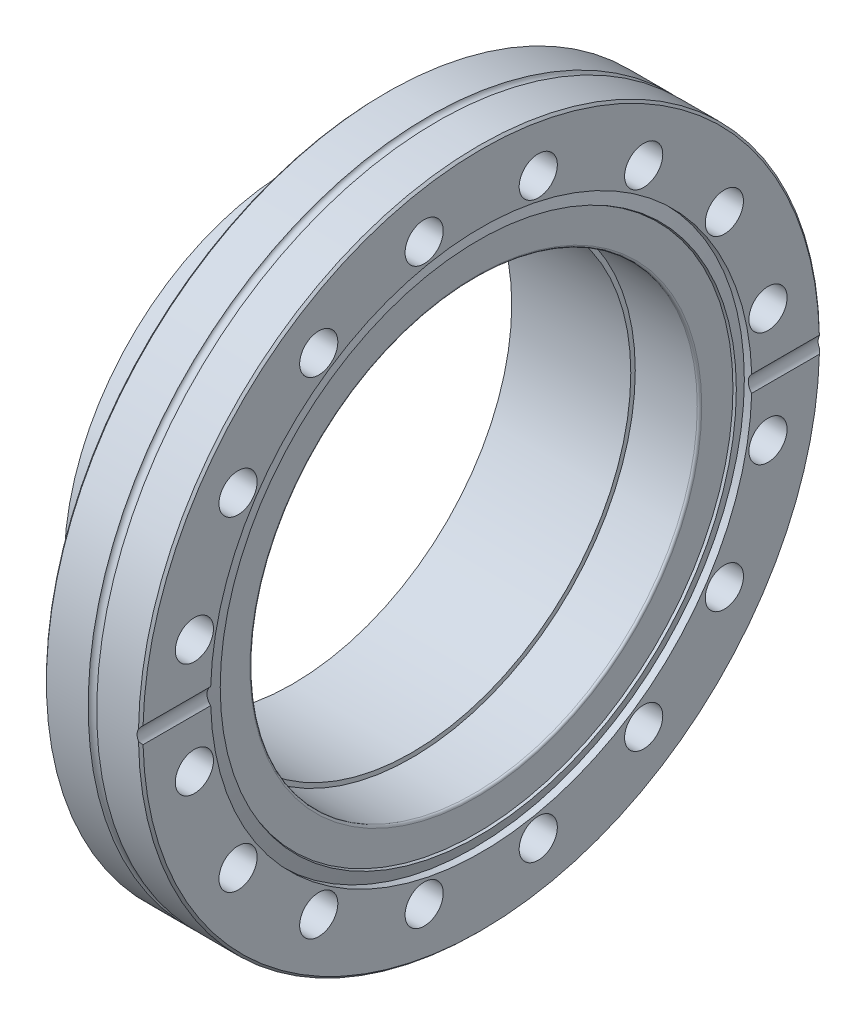
SolidWorks part; units mm, degrees
material "AISI 304"
ref_plane "Спереди" through (0, 0, 0) normal (0, 0, 1) x (1, 0, 0)
ref_plane "Сверху" through (0, 0, 0) normal (0, 1, 0) x (1, 0, 0)
ref_plane "Справа" through (0, 0, 0) normal (1, 0, 0) x (0, 0, -1)
ref_axis "Ось1" through (-110.1507, 0, 0) along (1, 0, 0)
sketch "Эскиз1" plane through (0, 0, 0) normal (0, 0, 1) x (1, 0, 0)
  line L0 (0, 75.8) -> (0, 0) construction
  line L1 (0, 0) -> (-21.85, 0) construction
  line L2 (-21.35, 75.8) -> (-12.0539, 75.8)
  line L3 (-0.35, 75.3) -> (-0.35, 60.25)
  line L4 (-0.35, 60.25) -> (-2.0191, 60.25)
  line L5 (-2.0191, 60.25) -> (-1, 57.45)
  line L6 (-1, 57.45) -> (-1.55, 57.2498)
  line L7 (-1.55, 57.2498) -> (-1.55, 50.3)
  line L8 (-2.05, 49.8) -> (-15.85, 49.8)
  line L9 (-15.85, 49.8) -> (-15.85, 51)
  line L10 (-15.85, 51) -> (-21.85, 51)
  line L11 (-21.85, 51) -> (-21.85, 75.3)
  line L12 (-10.1461, 75.8) -> (-0.85, 75.8)
  line L13 (-21.85, 75.3) -> (-21.35, 75.8)
  line L14 (-0.85, 75.8) -> (-0.35, 75.3)
  line L15 (-21.85, 65.1) -> (-0.35, 65.1) construction
  line L16 (-15.85, 50.8) -> (-135.35, 50.8)
  line L17 (-135.35, 50.8) -> (-135.35, 48.8)
  line L18 (-135.35, 48.8) -> (-15.85, 48.8)
  line L19 (-15.85, 48.8) -> (-15.85, 49.8)
  arc A0 (-12.0539, 75.8) -> (-10.1461, 75.8) centre (-11.1, 76.1) ccw
  arc A1 (-1.55, 50.3) -> (-2.05, 49.8) centre (-2.05, 50.3) cw
  point P4 (-21.85, 75.8)
  point P5 (-0.35, 75.8)
  point P14 (-21.85, 51)
  dimension "D2" = 1
  dimension "D18" = 0.5
  dimension "D1" = 151.6
  dimension "D3" = 10.75
  dimension "D4" = 0.3
  dimension "D5" = 21.5
  dimension "D6" = 102
  dimension "D7" = 6
  dimension "D8" = 20
  dimension "D9" = 120.5
  dimension "D10" = 0.65
  dimension "D11" = 114.9
  dimension "D12" = 1.2
  dimension "D13" = 99.6
  dimension "D14" = 0.5
  dimension "D15" = 45
  dimension "D16" = 0.5
  dimension "D17" = 45
  dimension "D19" = 101.6
  dimension "D20" = 135
  dimension "D21" = 130.2
  dimension "D22" = 2
  dimension "D23" = 2
revolve "Повернуть2" add sketch "Эскиз1" angle 360 about L1 region at (-11.2305, 63.1166, 0)
sketch "Эскиз7" plane through (-0.35, 0, 0) normal (1, 0, 0) x (0, 0, -1)
  line L0 (0, 0) -> (0, 65.1) construction
  line L1 (12.7004, 63.8491) -> (0, 0) construction
  circle A0 centre (0, 0) radius 65.1
  dimension "D1" = 11.25
hole_wizard "Отверстие с зазором M81" positions "Эскиз3" profile "Эскиз2" hole size "M8" standard "DIN" end condition through all
sketch "Эскиз3" plane through (-0.35, 0, 0) normal (1, 0, 0) x (0, 0, -1)
  point P3 (12.7004, 63.8491)
sketch "Эскиз2" plane through (-0.35, 63.8491, -12.7004) normal (0, 1, 0) x (0, 0, -1)
  line L0 (0, 0) -> (0, 21.5)
  line L1 (0, 21.5) -> (4.275, 21.5)
  line L2 (4.25, 21.475) -> (4.25, 0)
  line L5 (4.25, 0) -> (0, 0)
  line L7 (4.275, 21.5) -> (4.25, 21.475)
  line L8 (-4.275, 21.5) -> (-4.25, 21.475) construction
  line L11 (0, -6.35) -> (0, 107.95) construction
  dimension "Диаметр сквозного отверстия" = 8.5
  dimension "Глубина сквозного отверстия" = 21.5
  dimension "Диаметр задней зенковки" = 8.55
  dimension "Угол задней зенковки" = 90
pattern_circular "Круговой массив1" count 16 over 360 about axis through (-110.1507, 0, 0) along (1, 0, 0) of "Отверстие с зазором M81"
ref_plane "Плоскость1" through (0, 0, -75.8) normal (0, 0, -1) x (-1, 0, 0)
sketch "Эскиз6" plane through (0, 0, -75.8) normal (0, 0, -1) x (-1, 0, 0)
  line L0 (1.15, 0) -> (-3.85, 0) construction
  line L1 (0, 0) -> (21.85, 0) construction
  line L2 (0.35, 75.3) -> (0.35, 60.25) construction
  circle A0 centre (-1.35, 0) radius 2.5
  dimension "D1" = 5
  dimension "D2" = 0.8
extrude "Вырез-Вытянуть1" cut sketch "Эскиз6" against normal blind 17
pattern_circular "Круговой массив2" count 2 over 360 about axis through (-110.1507, 0, 0) along (1, 0, 0) of "Вырез-Вытянуть1"
revolve "Повернуть3" add sketch "Эскиз1<5>" angle 360 about L1 region at (-75.6, 49.8, 0)
sketch "Эскиз1<5>" plane through (0, 0, 0) normal (0, 0, 1) x (1, 0, 0) same geometry as "Эскиз1"
sketch "Эскиз8" plane through (0, 0, 0) normal (0, 0, 1) x (1, 0, 0)
  line L0 (-135.35, 48.8) -> (-15.85, 48.8) construction
  line L1 (-15.85, 50.8) -> (-135.35, 50.8) construction
  line L2 (-135.35, 50.8) -> (-135.35, 48.8) construction
  line L3 (-135.35, 48.8) -> (-42.35, 48.8)
  line L4 (-42.35, 50.8) -> (-135.35, 50.8)
  line L5 (-135.35, 50.8) -> (-135.35, 48.8)
  line L6 (-42.35, 50.8) -> (-42.35, 48.8)
  line L7 (-0.35, 75.3) -> (-0.35, 60.25) construction
  line L8 (0, 0) -> (-174.4224, 0) construction
  dimension "D1" = 42
revolve "Вырез-Повернуть1" cut sketch "Эскиз8" angle 360 about L8
